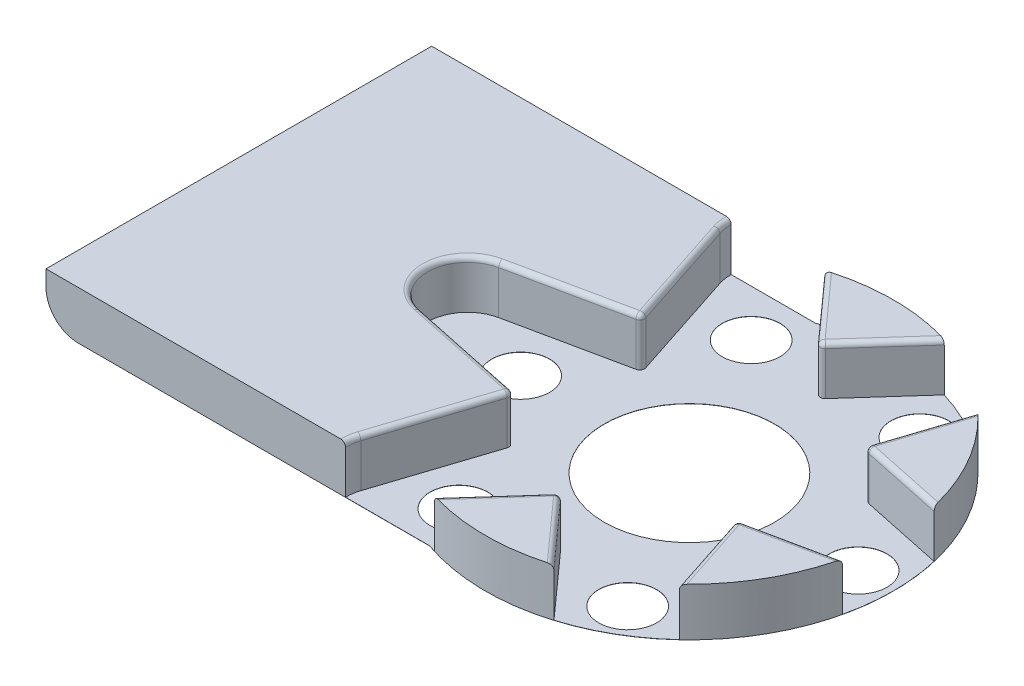
SolidWorks part; units mm, degrees
ref_plane "Alzado" through (0, 0, 0) normal (0, 0, 1) x (1, 0, 0)
ref_plane "Planta" through (0, 0, 0) normal (0, 1, 0) x (1, 0, 0)
ref_plane "Vista lateral" through (0, 0, 0) normal (1, 0, 0) x (0, 0, -1)
sketch "Croquis1" plane through (0, 0, 0) normal (0, 1, 0) x (1, 0, 0)
  line L0 (-28.04, 12) -> (-4.1581, 12)
  line L1 (-28.04, -12) -> (-4.1581, -12)
  line L2 (-28.04, 12) -> (-28.04, -12)
  line L3 (-28.04, 0) -> (0, 0) construction
  arc A0 (-4.1581, -12) -> (-4.1581, 12) centre (0, 0) ccw
  circle A1 centre (0, 0) radius 5.3
  dimension "D1" = 25.4
  dimension "D3" = 10.6
  dimension "D2" = 24
  dimension "D4" = 28.04
extrude "Saliente-Extruir1" add sketch "Croquis1" along normal blind 3
sketch "Croquis2" plane through (0, 3, 0) normal (0, 1, 0) x (1, 0, 0)
  line L0 (0, 0) -> (-13.8, 0) construction
  line L1 (-14.3146, -2.4465) -> (-6.9282, -4)
  line L2 (-14.3146, 2.4465) -> (-6.9282, 4)
  line L3 (-5.0386, 13.62) -> (0, 8)
  line L4 (-9.276, 11.1735) -> (-6.9282, 4)
  line L5 (9.276, 11.1735) -> (6.9282, 4)
  line L6 (5.0386, 13.62) -> (0, 8)
  line L7 (14.3146, -2.4465) -> (6.9282, -4)
  line L8 (14.3146, 2.4465) -> (6.9282, 4)
  line L9 (5.0386, -13.62) -> (0, -8)
  line L10 (9.276, -11.1735) -> (6.9282, -4)
  line L11 (-9.276, -11.1735) -> (-6.9282, -4)
  line L12 (-5.0386, -13.62) -> (0, -8)
  circle A0 centre (0, 0) radius 13.8 construction
  circle A1 centre (0, 0) radius 8 construction
  arc A2 (-14.3146, 2.4465) -> (-14.3146, -2.4465) centre (-13.8, 0) ccw
  arc A3 (-5.0386, 13.62) -> (-9.276, 11.1735) centre (-6.9, 11.9512) ccw
  arc A4 (9.276, 11.1735) -> (5.0386, 13.62) centre (6.9, 11.9512) ccw
  arc A5 (14.3146, -2.4465) -> (14.3146, 2.4465) centre (13.8, 0) ccw
  arc A6 (5.0386, -13.62) -> (9.276, -11.1735) centre (6.9, -11.9512) ccw
  arc A7 (-9.276, -11.1735) -> (-5.0386, -13.62) centre (-6.9, -11.9512) ccw
  circle A8 centre (0, 0) radius 16.3 construction
  point P43 (0, 0)
  dimension "D1" = 16
  dimension "D2" = 5
  dimension "D4" = 32.6
  dimension "D3" = 6
extrude "Cortar-Extruir2" cut sketch "Croquis2" against normal offset from surface (2.99 mm away) 0.01 up to face at (-11.8845, 0, 0)
fillet "Redondeo1" radius 2 1 edges at (-28.04, 0, 0)
fillet "Redondeo2" radius 0.3 21 edges at (-10.6214, 3, 3.2232) (6.9282, 1.505, 4) (-6.9282, 1.505, -4) (-6.9282, 1.505, 4) (0, 1.505, 8) (0, 1.505, -8) (6.9282, 1.505, -4) (9.6516, 3, 3.4272) (7.7939, 3, 6.645) (1.8578, 3, 10.0722) (9.6516, 3, -3.4272) (7.7939, 3, -6.645) (1.8578, 3, -10.0722) (-1.8578, 3, -10.0722) (-9.3725, 3, -11.5816) (-9.3725, 3, 11.5816) (-8.1021, 3, 7.5868) (-1.8578, 3, 10.0722) (-8.1021, 3, -7.5868) (-10.6214, 3, -3.2232) (-16.3, 3, 0)
sketch "Croquis3" plane through (0, 0, 0) normal (0, -1, 0) x (1, 0, 0)
  circle A0 centre (0, 0) radius 10.5 construction
  circle A1 centre (10.5, 0) radius 1.8
  dimension "D1" = 21
  dimension "D2" = 3.6
extrude "Cortar-Extruir3" cut sketch "Croquis3" against normal blind 10
pattern_circular "MatrizC1" count 6 over 360 about axis through (0, 0, 0) along (0, 1, 0) of "Cortar-Extruir3"
